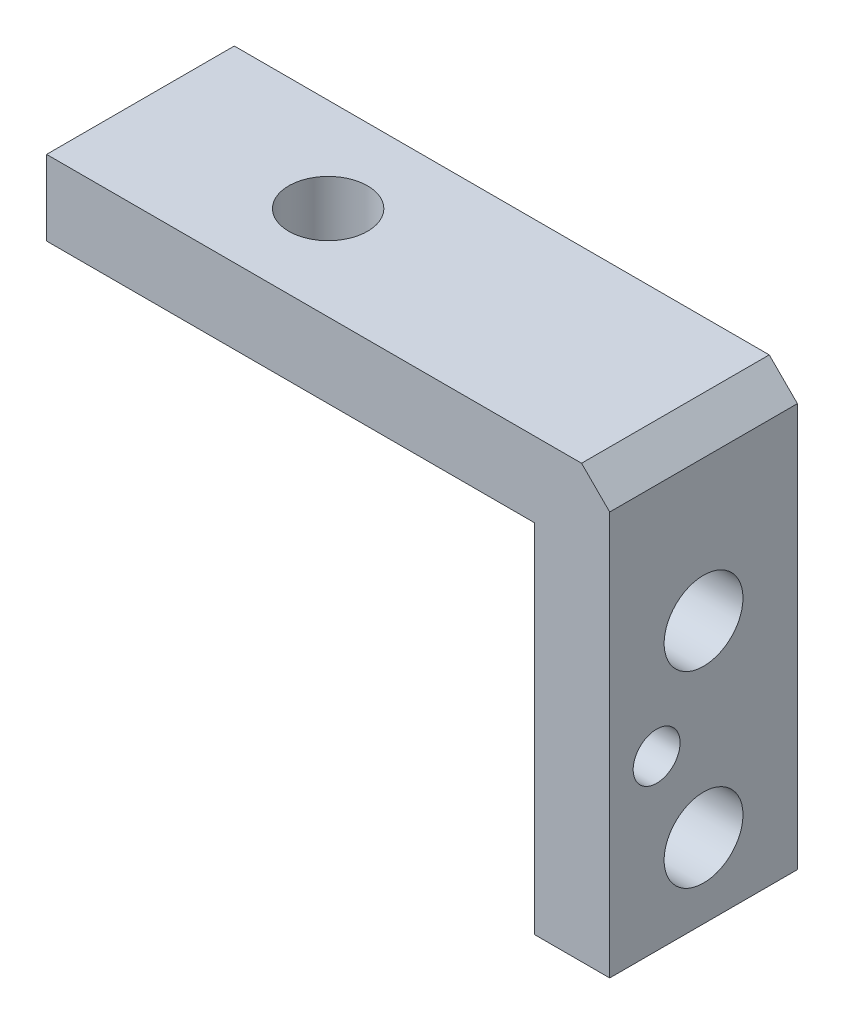
SolidWorks part; units mm, degrees
material "1060 Alloy"
ref_plane "Front Plane" through (0, 0, 0) normal (0, 0, 1) x (1, 0, 0)
ref_plane "Top Plane" through (0, 0, 0) normal (0, 1, 0) x (1, 0, 0)
ref_plane "Right Plane" through (0, 0, 0) normal (1, 0, 0) x (0, 0, -1)
sketch "Sketch1" plane through (0, 0, 0) normal (0, 0, 1) x (1, 0, 0)
  line L1 (15, -11.5) -> (-15, -11.5)
  line L2 (15, -11.5) -> (15, 11.5)
  line L3 (15, 11.5) -> (-15, 11.5)
  line L4 (-15, -11.5) -> (-15, 11.5)
  line L5 (15, -11.5) -> (-15, 11.5) construction
  line L6 (15, 11.5) -> (-15, -11.5) construction
  point P0 (0, 0)
  dimension "D1" = 30
  dimension "D2" = 23
extrude "Boss-Extrude1" add sketch "Sketch1" along normal mid plane 10
sketch "Sketch2" plane through (0, 0, 5) normal (0, 0, 1) x (1, 0, 0)
  line L1 (-15, -11.5) -> (11, -11.5)
  line L2 (-15, -11.5) -> (-15, 7.5)
  line L3 (-15, 7.5) -> (11, 7.5)
  line L4 (11, -11.5) -> (11, 7.5)
  line L5 (-15, -11.5) -> (11, 7.5) construction
  line L6 (-15, 7.5) -> (11, -11.5) construction
  point P4 (-2, -2)
  dimension "D1" = 19
  dimension "D2" = 26
extrude "Cut-Extrude1" cut sketch "Sketch2" against normal through all
chamfer "Chamfer1" distance 1.5 angle 45 1 edges at (15, 11.5, 0)
hole_wizard "Tapped Hole for M4x0.7 Helicoil1" positions "Sketch3" profile "Sketch4" tap size "M4x0.7" standard "Helicoil® Metric" end condition through all
sketch "Sketch3" plane through (0, 11.5, 0) normal (0, 1, 0) x (1, 0, 0)
  line L0 (-15, -5) -> (-15, 5) construction
  point P0 (-5, 0)
  dimension "D1" = 10
sketch "Sketch4" plane through (-5, 11.5, 0) normal (1, 0, 0) x (0, 0, 1)
  line L0 (0, 0) -> (0, 23)
  line L1 (0, 23) -> (2.1, 23)
  line L2 (2.1, 23) -> (2.1, 0)
  line L5 (2.1, 0) -> (0, 0)
  line L11 (0, -6.35) -> (0, 107.95) construction
  dimension "Thru Tap Drill Dia." = 4.2
  dimension "Thru Tap Drill Depth" = 23
cosmetic thread "Hole Thread1" parameters "D1"=4, "D2"=5.007
ref_axis "Axis1" through (-5, 7.5, 0) along (0, 1, 0)
ref_plane "Plane1" through (-5, 0, 0) normal (-1, 0, 0) x (0, 0, 1)
hole_wizard "M4 Clearance Hole1" positions "Sketch5" profile "Sketch6" hole size "M4" standard "ISO" end condition through all
sketch "Sketch5" plane through (15, 0, 0) normal (1, 0, 0) x (0, 0, -1)
  point P0 (0, -7.517)
  point P3 (0, 2.483)
sketch "Sketch6" plane through (15, -7.517, 0) normal (0, 1, 0) x (0, 0, -1)
  line L0 (0, 0) -> (0, 30)
  line L1 (0, 30) -> (2.1, 30)
  line L2 (2.1, 30) -> (2.1, 0)
  line L5 (2.1, 0) -> (0, 0)
  line L11 (0, -6.35) -> (0, 107.95) construction
  dimension "Thru Hole Dia." = 4.2
  dimension "Thru Hole Depth" = 30
hole_wizard "M3 Tapped Hole1" positions "Sketch7" profile "Sketch8" tap size "M3" standard "ISO" end condition through all
sketch "Sketch7" plane through (15, 0, 0) normal (1, 0, 0) x (0, 0, -1)
  line L1 (0, 2.483) -> (0, -7.517) construction
  line L2 (0, -2.517) -> (-2.5, -2.517) construction
  point P0 (-2.5, -2.517)
  dimension "D1" = 2.5
sketch "Sketch8" plane through (15, -2.517, 2.5) normal (0, 1, 0) x (0, 0, -1)
  line L0 (0, 0) -> (0, 30)
  line L1 (0, 30) -> (1.25, 30)
  line L2 (1.25, 30) -> (1.25, 0)
  line L5 (1.25, 0) -> (0, 0)
  line L11 (0, -6.35) -> (0, 107.95) construction
  dimension "Thru Tap Drill Dia." = 2.5
  dimension "Thru Tap Drill Depth" = 30
cosmetic thread "Hole Thread2" parameters "D2"=3
